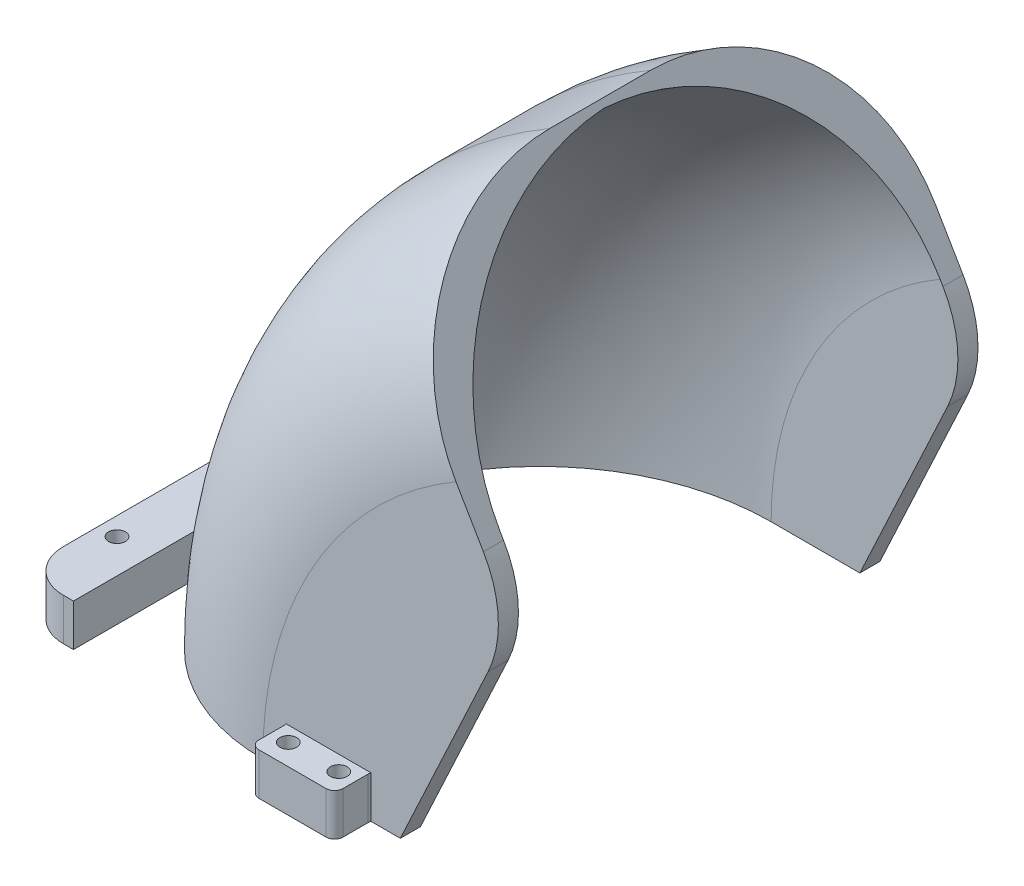
SolidWorks part; units mm, degrees
material "ABS PC"
ref_plane "Front Plane" through (0, 0, 0) normal (0, 0, 1) x (1, 0, 0)
ref_plane "Top Plane" through (0, 0, 0) normal (0, 1, 0) x (1, 0, 0)
ref_plane "Right Plane" through (0, 0, 0) normal (1, 0, 0) x (0, 0, -1)
sketch "Sketch1" plane through (0, 0, 0) normal (0, 0, 1) x (1, 0, 0)
  line L4 (-137.69, 0) -> (-136.1, 0)
  line L5 (-136.1, 0) -> (-38.1, 0) construction
  line L6 (-68.6843, 117.4976) -> (-69.4867, 118.8703)
  circle A0 centre (0, 0) radius 38.1 construction
  arc A1 (-68.6843, 117.4976) -> (-136.1, 0) centre (0, 0) ccw
  arc A2 (-69.4867, 118.8703) -> (-137.69, 0) centre (0, 0) ccw
  circle A3 centre (0, 0) radius 137.69 construction
  circle A4 centre (0, 0) radius 136.1 construction
  dimension "D1" = 76.2
  dimension "D2" = 1.59
  dimension "D4" = 98
extrude "Boss-Extrude1" add sketch "Sketch1" along normal blind 104.45
sketch "Sketch2" plane through (0, 0, 104.45) normal (0, 0, 1) x (1, 0, 0)
  line L0 (-137.69, 0) -> (0, 0)
  line L1 (0, 0) -> (-69.4867, 118.8703)
  line L2 (-137.69, 0) -> (-136.1, 0)
  line L3 (-68.6843, 117.4976) -> (-69.4867, 118.8703)
  arc A2 (-69.4867, 118.8703) -> (-137.69, 0) centre (0, 0) ccw
  arc A3 (-68.6843, 117.4976) -> (-136.1, 0) centre (0, 0) ccw
  arc A4 (-69.4867, 118.8703) -> (-137.69, 0) centre (0, 0) ccw
  dimension "D1" = 0
extrude "Boss-Extrude2" add sketch "Sketch2" along normal blind 4.7752
sketch "Sketch3" plane through (0, 0, 0) normal (0, 0, -1) x (-1, 0, 0)
  line L2 (0, 0) -> (137.69, 0)
  line L3 (69.4867, 118.8703) -> (0, 0)
  line L4 (0, 0) -> (137.69, 0)
  line L5 (69.4867, 118.8703) -> (0, 0)
  arc A1 (137.69, 0) -> (69.4867, 118.8703) centre (0, 0) ccw
  arc A2 (137.69, 0) -> (69.4867, 118.8703) centre (0, 0) ccw
  dimension "D1" = 0
extrude "Boss-Extrude3" add sketch "Sketch3" along normal blind 4.7752
sketch "Sketch4" plane through (0, 0, 0) normal (0, -1, 0) x (1, 0, 0)
  line L1 (-136.1, 109.2252) -> (-150.1, 109.2252)
  line L2 (-136.1, 109.2252) -> (-136.1, -1.9248)
  line L3 (-136.1, -1.9248) -> (-150.1, -1.9248)
  line L4 (-150.1, 109.2252) -> (-150.1, -1.9248)
  line L6 (-137.69, 109.2252) -> (0, 109.2252) construction
  line L7 (-136.1, 104.45) -> (-136.1, 0) construction
  line L12 (-69.0597, 117.8) -> (-85.0597, 117.8)
  line L13 (-87.0597, 115.8) -> (-87.0597, 109.7987)
  line L14 (-88.6859, 107.8) -> (-65.0597, 107.8)
  line L15 (-67.0597, 109.8) -> (-67.0597, 115.8)
  line L16 (-69.0597, 117.8) -> (-85.0597, 117.8)
  line L17 (-87.0597, 115.8) -> (-87.0597, 109.7987)
  line L18 (-88.6859, 107.8) -> (-65.0597, 107.8)
  line L19 (-67.0597, 109.8) -> (-67.0597, 115.8)
  line L20 (-87.0597, -8.1987) -> (-87.0597, -14.2)
  line L21 (-85.0597, -16.2) -> (-69.0597, -16.2)
  line L22 (-67.0597, -14.2) -> (-67.0597, -8.2)
  line L23 (-65.0597, -6.2) -> (-88.6859, -6.2)
  line L24 (-87.0597, -8.1987) -> (-87.0597, -14.2)
  line L25 (-85.0597, -16.2) -> (-69.0597, -16.2)
  line L26 (-67.0597, -14.2) -> (-67.0597, -8.2)
  line L27 (-65.0597, -6.2) -> (-88.6859, -6.2)
  circle A0 centre (-71.0597, -11.2) radius 2 construction
  circle A1 centre (-71.0597, -11.2) radius 2
  circle A2 centre (-83.0597, -11.2) radius 2 construction
  circle A3 centre (-83.0597, -11.2) radius 2
  arc A4 (-85.0597, 117.8) -> (-87.0597, 115.8) centre (-85.0597, 115.8) ccw
  arc A5 (-89.0457, 107.7987) -> (-87.0597, 109.7987) centre (-89.0597, 109.7987) ccw
  arc A6 (-67.0597, 109.8) -> (-65.0597, 107.8) centre (-65.0597, 109.8) ccw
  arc A7 (-67.0597, 115.8) -> (-69.0597, 117.8) centre (-69.0597, 115.8) ccw
  arc A8 (-85.0597, 117.8) -> (-87.0597, 115.8) centre (-85.0597, 115.8) ccw
  arc A9 (-89.0457, 107.7987) -> (-87.0597, 109.7987) centre (-89.0597, 109.7987) ccw
  arc A10 (-67.0597, 109.8) -> (-65.0597, 107.8) centre (-65.0597, 109.8) ccw
  arc A11 (-67.0597, 115.8) -> (-69.0597, 117.8) centre (-69.0597, 115.8) ccw
  arc A12 (-87.0597, -14.2) -> (-85.0597, -16.2) centre (-85.0597, -14.2) ccw
  arc A13 (-69.0597, -16.2) -> (-67.0597, -14.2) centre (-69.0597, -14.2) ccw
  arc A14 (-65.0597, -6.2) -> (-67.0597, -8.2) centre (-65.0597, -8.2) ccw
  arc A15 (-87.0597, -8.1987) -> (-89.0457, -6.1987) centre (-89.0597, -8.1987) ccw
  arc A16 (-87.0597, -14.2) -> (-85.0597, -16.2) centre (-85.0597, -14.2) ccw
  arc A17 (-69.0597, -16.2) -> (-67.0597, -14.2) centre (-69.0597, -14.2) ccw
  arc A18 (-65.0597, -6.2) -> (-67.0597, -8.2) centre (-65.0597, -8.2) ccw
  arc A19 (-87.0597, -8.1987) -> (-89.0457, -6.1987) centre (-89.0597, -8.1987) ccw
  circle A20 centre (-71.0597, 112.8) radius 2 construction
  circle A21 centre (-71.0597, 112.8) radius 2
  circle A22 centre (-83.0597, 112.8) radius 2 construction
  circle A23 centre (-83.0597, 112.8) radius 2
  circle A24 centre (-145.767, 90.8) radius 2 construction
  circle A25 centre (-145.767, 90.8) radius 2
  circle A26 centre (-145.767, 66.8) radius 2 construction
  circle A27 centre (-145.767, 66.8) radius 2
  arc A32 (-145.767, 0.8) -> (-145.767, 4.8) centre (-145.767, 2.8) ccw construction
  arc A33 (-145.767, 0.8) -> (-145.767, 4.8) centre (-145.767, 2.8) ccw construction
  circle A34 centre (-145.767, 18.8) radius 2 construction
  circle A35 centre (-145.767, 18.8) radius 2
  circle A36 centre (-145.767, 2.8) radius 8.8142
  ellipse E1 centre (-88.6859, 59.8) end of major axis (-138.3791, 59.8) minor radius 48 (-88.6859, 107.8) -> (-89.0457, 107.7987) ccw
  ellipse E2 centre (-88.6859, 59.8) end of major axis (-138.3791, 59.8) minor radius 48 (-88.6859, 107.8) -> (-89.0457, 107.7987) ccw
  ellipse E3 centre (-88.6859, 41.8) end of major axis (-38.9926, 41.8) minor radius 48 (-89.0457, -6.1987) -> (-88.6859, -6.2) ccw
  ellipse E4 centre (-88.6859, 41.8) end of major axis (-38.9926, 41.8) minor radius 48 (-89.0457, -6.1987) -> (-88.6859, -6.2) ccw
  line M5 (-137.69, 109.2252) -> (-137.69, -4.7752)
  line M12 (0, 109.2252) -> (-137.69, 109.2252)
  dimension "D1" = 111.15
  dimension "D2" = 14
  dimension "D3" = 0
  dimension "D4" = 0
extrude "Boss-Extrude4" add sketch "Sketch4" against normal blind 10 contours A36 L1 L4 A35 A27 A25 M5 | L19 A11 L16 A8 L17 A9 A10 A23 A21 M12 | L3 A36 L4 M5 | E4 A19 L24 A16 L25 A17 L26 A18 L27 A3 A1 | E2 L18 A10 A9 M12 region at (-77.0597, 0, 113.5899) region at (-77.0588, 0, 108.4966) region at (-143.799, 0, 59.9002) region at (-144.1902, 0, 4.3812) region at (-77.0595, 0, -11.1107)
fillet "Fillet1" radius 10 2 edges at (-150.1, 5, -1.9248) (-150.1, 5, 109.2252)
fillet "Fillet3" radius 55 2 edges at (-118.049, 67.7321, 104.45) (-118.049, 67.7321, 0)
fillet "Fillet4" radius 45 2 edges at (-119.4281, 68.5234, -4.7752) (-119.4281, 68.5234, 109.2252)
chamfer "Chamfer1" distance 60 angle 65 2 edges at (0, 0, -2.3876) (0, 0, 106.8376) first distance on face at (-74.4722, 0, 77.9235)
fillet "Fillet5" radius 26 2 edges at (-33.3758, 57.0957, -2.3876) (-33.3758, 57.0957, 106.8376)
